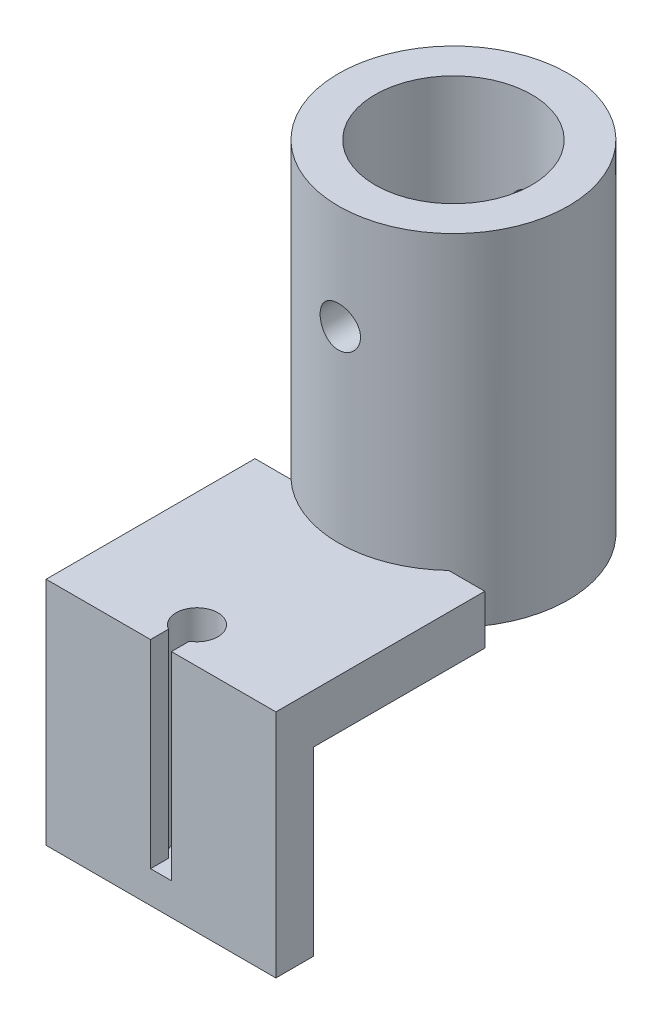
SolidWorks part; units mm, degrees
ref_plane "前基準面" through (0, 0, 0) normal (0, 0, 1) x (1, 0, 0)
ref_plane "上基準面" through (0, 0, 0) normal (0, 1, 0) x (1, 0, 0)
ref_plane "右基準面" through (0, 0, 0) normal (1, 0, 0) x (0, 0, -1)
sketch "草圖1" plane through (0, 0, 0) normal (0, 1, 0) x (1, 0, 0)
  circle A0 centre (0, 0) radius 11
  dimension "D1" = 22
extrude "填料-伸長1" add sketch "草圖1" along normal blind 50
sketch "草圖2" plane through (0, 50, 0) normal (0, 1, 0) x (1, 0, 0)
  circle A0 centre (0, 0) radius 7.5
  dimension "D1" = 15
extrude "除料-伸長1" cut sketch "草圖2" against normal through all
ref_plane "平面1" through (0, 0, 18) normal (0, 0, 1) x (1, 0, 0)
sketch "草圖4" plane through (0, 0, 18) normal (0, 0, 1) x (1, 0, 0)
  line L0 (0, 50) -> (0, 30) construction
  line L1 (7.5, 50) -> (-7.5, 50) construction
  circle A1 centre (0, 40) radius 1.935
  dimension "D3" = 3.87
  dimension "D1" = 20
extrude "除料-伸長4" cut sketch "草圖4" against normal blind 50
ref_plane "平面2" through (11, 0, 0) normal (1, 0, 0) x (0, 0, -1)
sketch "草圖6" plane through (0, 0, 18) normal (0, 0, 1) x (1, 0, 0)
  line L0 (0, 38.065) -> (0, 22.065) construction
  circle A0 centre (0, 40) radius 1.935 construction
  dimension "D1" = 16
sketch "草圖11" plane through (0, 0, 18) normal (0, 0, 1) x (1, 0, 0)
  line L0 (-11, 22.065) -> (11, 22.065)
  line L1 (-11, 50) -> (-11, 0) construction
  line L2 (11, 22.065) -> (11, 0)
  line L3 (11, -33.6925) -> (11, 33.6925) construction
  line L4 (11, 0) -> (-11, 0)
  line L5 (-11, 0) -> (-11, 22.065)
extrude "填料-伸長2" add sketch "草圖11" along normal blind 10 and the other way blind 10
sketch "草圖35" plane through (0, 22.065, 0) normal (0, 1, 0) x (1, 0, 0)
  line L0 (11, -28) -> (-11, -28) construction
  line L1 (-1, -25.5521) -> (1, -25.5521)
  line L2 (-1, -25.5521) -> (-1, -30.4479)
  line L3 (-1, -30.4479) -> (1, -30.4479)
  line L4 (1, -25.5521) -> (1, -30.4479)
  line L5 (-1, -25.5521) -> (1, -30.4479) construction
  line L6 (-1, -30.4479) -> (1, -25.5521) construction
  point P0 (0, -28)
  dimension "D1" = 2
extrude "除料-伸長5" cut sketch "草圖35" against normal blind 19
sketch "草圖36" plane through (0, 22.065, 0) normal (0, 1, 0) x (1, 0, 0)
  line L0 (0, -25.5521) -> (0, -24.5521) construction
  line L1 (1, -25.5521) -> (-1, -25.5521) construction
  circle A0 centre (0, -24.5521) radius 2
  dimension "D2" = 4
  dimension "D1" = 1
extrude "除料-伸長6" cut sketch "草圖36" against normal blind 19
sketch "草圖38" plane through (11, 0, 0) normal (1, 0, 0) x (0, 0, -1)
  line L1 (11.109, -0.5294) -> (-24.4134, -0.5294)
  line L2 (11.109, -0.5294) -> (11.109, 17.345)
  line L3 (11.109, 17.345) -> (-24.4134, 17.345)
  line L4 (-24.4134, -0.5294) -> (-24.4134, 17.345)
extrude "除料-伸長7" cut sketch "草圖38" against normal blind 29
